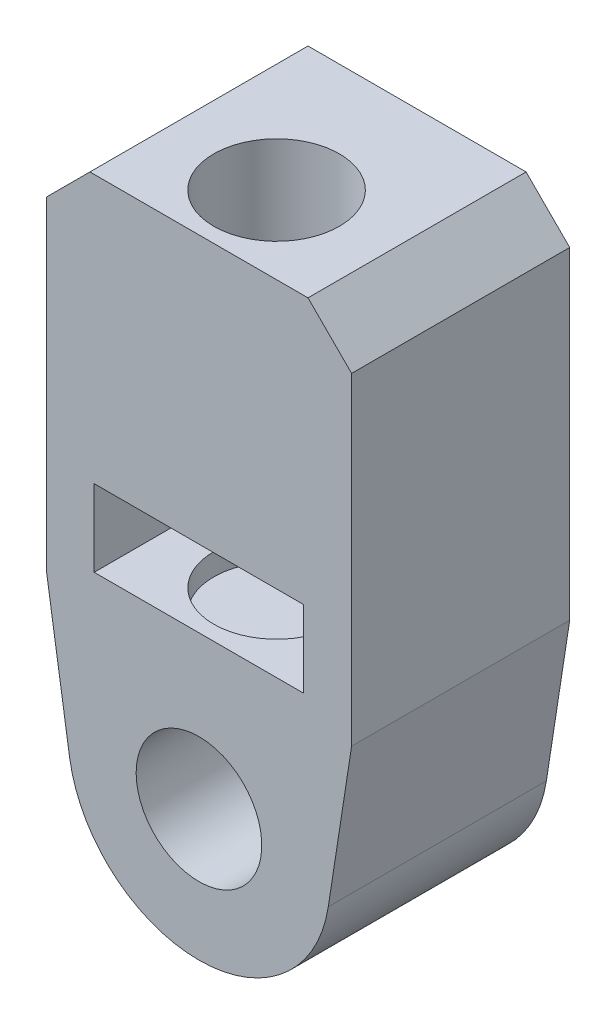
SolidWorks part; units mm, degrees
ref_plane "Front Plane" through (0, 0, 0) normal (0, 0, 1) x (1, 0, 0)
ref_plane "Top Plane" through (0, 0, 0) normal (0, 1, 0) x (1, 0, 0)
ref_plane "Right Plane" through (0, 0, 0) normal (1, 0, 0) x (0, 0, -1)
sketch "Sketch1" plane through (0, 0, 0) normal (0, 0, 1) x (1, 0, 0)
  line L0 (-5.5562, 4.7625) -> (-5.5562, 18.0975)
  line L1 (-5.5562, 18.0975) -> (5.5562, 18.0975)
  line L2 (5.5562, 18.0975) -> (5.5562, 4.7625)
  line L3 (-5.5562, 4.7625) -> (-4.7065, -0.7284)
  line L4 (4.7065, -0.7284) -> (5.5562, 4.7625)
  circle A1 centre (0, 0) radius 2.286
  arc A2 (-4.7065, -0.7284) -> (4.7065, -0.7284) centre (0, 0) ccw
  point P10 (0, 18.0975)
  dimension "D1" = 9.525
  dimension "D2" = 4.572
  dimension "D3" = 13.335
  dimension "D4" = 11.1125
  dimension "D5" = 4.7625
extrude "Boss-Extrude1" add sketch "Sketch1" along normal up to surface (7.9375 mm away)
sketch "Sketch2" plane through (0, 18.0975, 0) normal (0, 1, 0) x (1, 0, 0)
  circle A1 centre (0, -5.1125) radius 2.286
  circle A2 centre (0, -5.1125) radius 1.7525 construction
  dimension "D1" = 4.572
extrude "Cut-Extrude1" cut sketch "Sketch2" against normal offset from surface (13.335 mm away) 4.7625 up to plane "Top Plane"
sketch "Sketch3" plane through (0, 4.7625, 0) normal (0, 1, 0) x (1, 0, 0)
  line L11 (5.5563, -7.9375) -> (-5.5562, -7.9375) construction
  line L12 (-1.9064, -1.8105) -> (-3.8128, -5.1125)
  line L16 (3.8128, -5.1125) -> (1.9064, -1.8105)
  line L17 (1.9064, -1.8105) -> (-1.9064, -1.8105)
  line L18 (-3.8128, -5.1125) -> (-3.8128, -7.9375)
  line L19 (-3.8128, -7.9375) -> (3.8128, -7.9375)
  line L20 (3.8128, -7.9375) -> (3.8128, -5.1125)
  line L22 (-1.9064, -8.4145) -> (0, -8.4145) [skipped]
  line L23 (-3.8128, -5.1125) -> (-2.8596, -6.7635) [skipped]
  line L24 (2.1818, -7.9375) -> (2.8596, -6.7635) [skipped]
  circle A0 centre (0, -5.1125) radius 3.302 construction
  dimension "D1" = 6.604
extrude "Cut-Extrude2" cut sketch "Sketch3" along normal blind 2.794 from offset 0.7937
chamfer "Chamfer1" distance 1.5875 angle 45 2 edges at (5.5563, 18.0975, 3.9687) (-5.5562, 18.0975, 3.9687)
